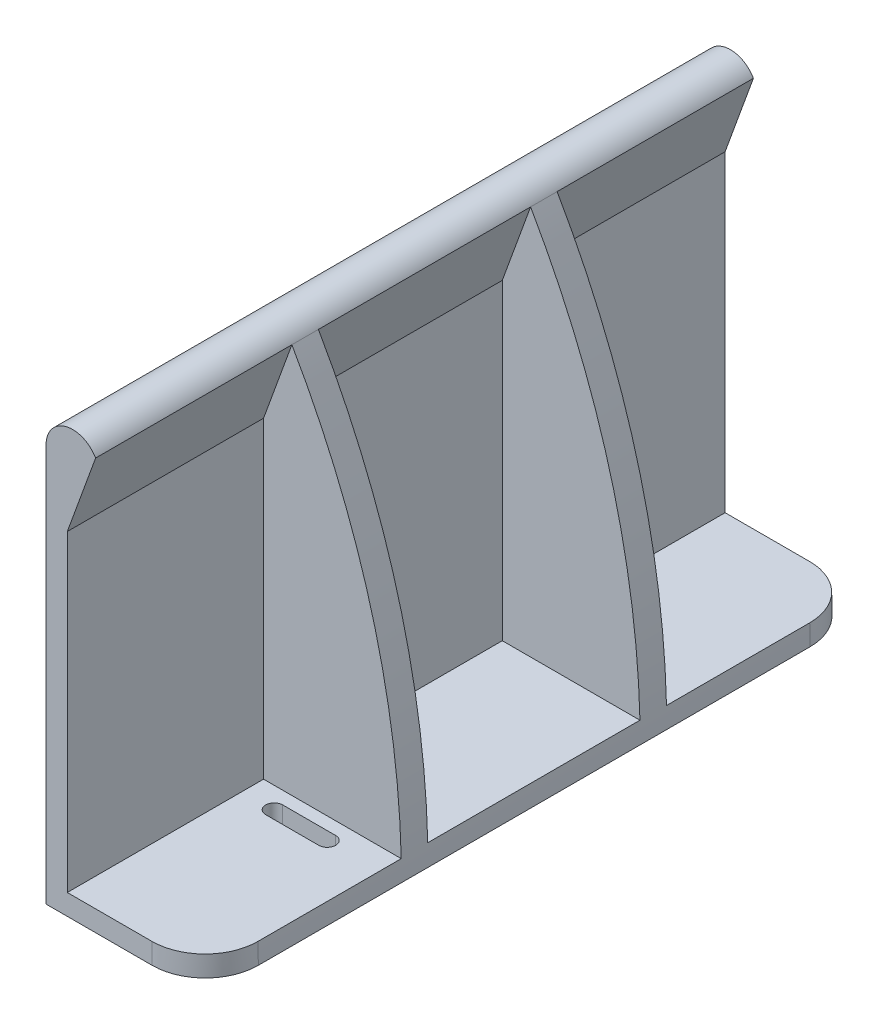
SolidWorks part; units mm, degrees
note: '?' marks a value the reader was unsure of.
ref_plane "Alzado" through (0, 0, 0) normal (0, 0, 1) x (1, 0, 0)
ref_plane "Planta" through (0, 0, 0) normal (0, 1, 0) x (1, 0, 0)
ref_plane "Vista lateral" through (0, 0, 0) normal (1, 0, 0) x (0, 0, -1)
sketch "Croquis1" plane through (0, 0, 0) normal (0, 0, 1) x (1, 0, 0)
  line L0 (0, 0) -> (61.1064, 0) construction
  line L1 (0, 10) -> (0, 43.4255) construction
  line L2 (0, 0) -> (0, 75)
  line L3 (30, 0) -> (0, 0)
  arc A0 (0, 75) -> (9.3361, 77.4896) centre (5, 75) cw
  arc A1 (9.3361, 77.4896) -> (30, 0) centre (-125.625, 0) cw
  dimension "D2" = 5
  dimension "D1" = 75
  dimension "D3" = 30
extrude "Saliente-Extruir1" add sketch "Croquis1" along normal mid plane 124
sketch "Croquis3" plane through (0, 0, 0) normal (0, 0, 1) x (1, 0, 0)
  line L0 (9.3361, 77.4896) -> (4, 62.8288)
  line L1 (4, 62.8288) -> (4, 4)
  line L2 (4, 4) -> (29.9486, 4)
  line L3 (29.9486, 4) -> (32.2284, 77.4896)
  line L4 (32.2284, 77.4896) -> (9.3361, 77.4896)
  line L5 (0, 75) -> (0, 0) construction
  line L6 (0, 0) -> (30, 0) construction
  arc A0 (30, 0) -> (9.3361, 77.4896) centre (-125.625, 0) ccw construction
  point P13 (32.2284, 77.4896)
  dimension "D1" = 4
  dimension "D2" = 4
  dimension "D3" = 160
extrude "Cortar-Extruir1" cut sketch "Croquis3" against normal mid plane 40
sketch "Croquis4" plane through (0, 0, 0) normal (0, 0, 1) x (1, 0, 0)
  line L0 (9.3361, 77.4896) -> (4, 62.8288)
  line L1 (4, 62.8288) -> (4, 3.9014)
  line L2 (4, 3.9014) -> (34.9289, 3.9014)
  line L3 (34.9289, 3.9014) -> (21.5679, 77.4896)
  line L4 (21.5679, 77.4896) -> (9.3361, 77.4896)
  point P2 (34.9289, 3.9014)
  point P3 (9.3361, 77.4896)
  dimension "D3" = 160
extrude "Cortar-Extruir2" cut sketch "Croquis4" along normal blind 124 from offset 25
mirror "Simetría1" about plane through (0, 0, 0) normal (0, 0, 1) of "Cortar-Extruir2"
sketch "Croquis5" plane through (0, 0, 0) normal (0, -1, 0) x (1, 0, 0)
  line L0 (1.2901, 0) -> (63.6935, 0) construction
  line L1 (10, 29) -> (20, 29) construction
  line L2 (10, 30.6) -> (20, 30.6)
  line L3 (10, 27.4) -> (20, 27.4)
  line L4 (0, 62) -> (0, -62) construction
  line L5 (10, -29) -> (20, -29) construction
  line L6 (10, -30.6) -> (20, -30.6)
  line L7 (10, -27.4) -> (20, -27.4)
  arc A0 (10, 30.6) -> (10, 27.4) centre (10, 29) ccw
  arc A1 (20, 27.4) -> (20, 30.6) centre (20, 29) ccw
  arc A2 (10, -30.6) -> (10, -27.4) centre (10, -29) cw
  arc A3 (20, -27.4) -> (20, -30.6) centre (20, -29) cw
  point P5 (15, 29)
  point P14 (15, -29)
  dimension "D1" = 1.6
  dimension "D2" = 29
  dimension "D3" = 10
  dimension "D4" = 10
extrude "Cortar-Extruir3" cut sketch "Croquis5" against normal up to surface (3.9014 mm away) up to face at (16.9755, 3.9014, 43.5)
fillet "Redondeo1" radius 10 2 edges at (29.9878, 1.9508, -62) (29.9878, 1.9508, 62)
fillet "Redondeo2" [suppressed] radius 2?
